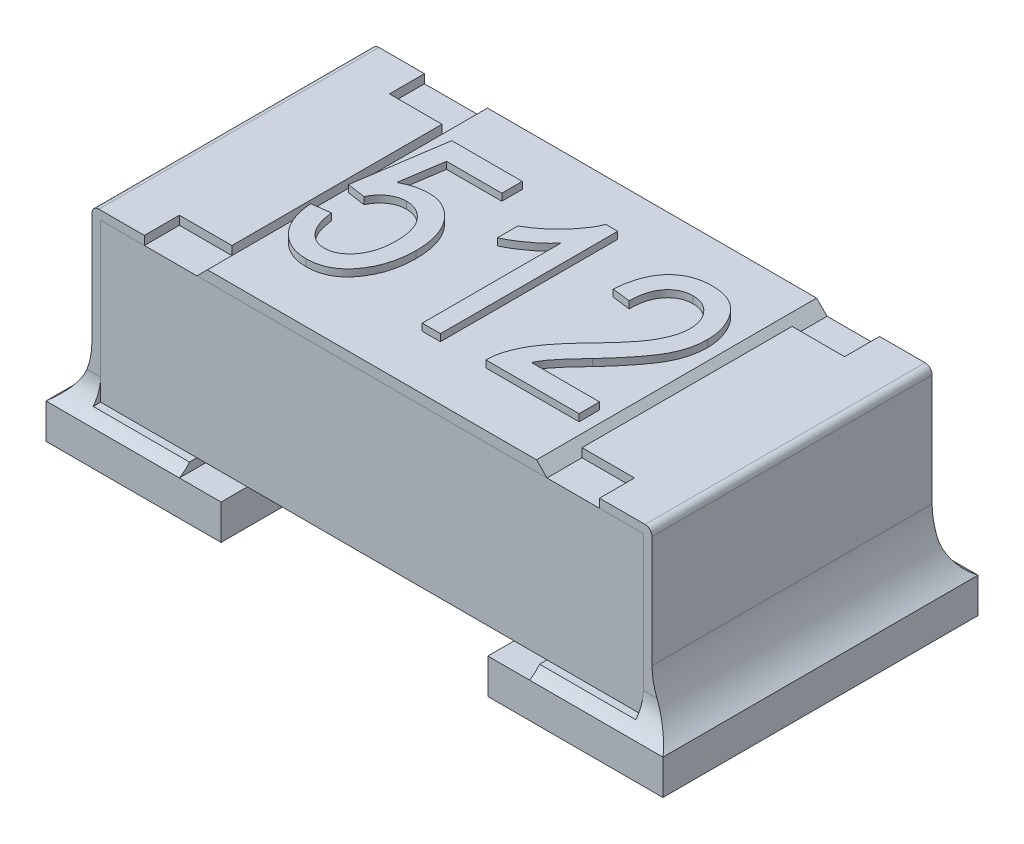
SolidWorks part; units mm, degrees
material "Ceramic Porcelain"
ref_plane "Front Plane" through (0, 0, 0) normal (0, 0, 1) x (1, 0, 0)
ref_plane "Top Plane" through (0, 0, 0) normal (0, 1, 0) x (1, 0, 0)
ref_plane "Right Plane" through (0, 0, 0) normal (1, 0, 0) x (0, 0, -1)
sketch "Sketch1" plane through (0, 0, 0) normal (1, 0, 0) x (0, 0, -1)
  line L0 (0, 55) -> (0, -55) construction
  line L1 (-0.4, 0.575) -> (0.4, 0.575)
  line L2 (-0.4, 0.575) -> (-0.4, 0.125)
  line L3 (-0.4, 0.125) -> (0.4, 0.125)
  line L4 (0.4, 0.575) -> (0.4, 0.125)
  line L5 (55, 0) -> (-55, 0) construction
  dimension "D1" = 0.8
  dimension "D2" = 0.4
  dimension "D3" = 0.45
  dimension "D4" = 0.125
extrude "Boss-Extrude1" add sketch "Sketch1" along normal mid plane 1.55
sketch "Sketch2" plane through (0, 0, 0) normal (0, 0, 1) x (1, 0, 0)
  line L0 (-0.5, 0.6) -> (-0.78, 0.6)
  line L1 (-0.8, 0.58) -> (-0.8, 0.1)
  line L2 (-0.8, 0.1) -> (-0.5, 0.1)
  line L3 (-0.5, 0.1) -> (-0.5, 0.125)
  line L4 (0.775, 0.125) -> (-0.775, 0.125) construction
  line L5 (-0.5, 0.125) -> (-0.775, 0.125)
  line L6 (-0.775, 0.125) -> (-0.775, 0.575)
  line L7 (-0.775, 0.575) -> (-0.5, 0.575)
  line L8 (0.775, 0.575) -> (-0.775, 0.575) construction
  line L9 (-0.5, 0.575) -> (-0.5, 0.6)
  line L11 (0.5, 0.575) -> (0.5, 0.6)
  line L12 (0.5, 0.6) -> (0.78, 0.6)
  line L13 (0.8, 0.58) -> (0.8, 0.1)
  line L14 (0.8, 0.1) -> (0.5, 0.1)
  line L15 (0.5, 0.1) -> (0.5, 0.125)
  line L16 (0.5, 0.125) -> (0.775, 0.125)
  line L17 (0.775, 0.125) -> (0.775, 0.575)
  line L18 (0.775, 0.575) -> (0.5, 0.575)
  arc A0 (0.78, 0.6) -> (0.8, 0.58) centre (0.78, 0.58) cw
  arc A1 (-0.78, 0.6) -> (-0.8, 0.58) centre (-0.78, 0.58) ccw
  point P28 (-0.8, 0.6)
  dimension "D6" = 0.02
  dimension "D1" = 0.025
  dimension "D2" = 0.025
  dimension "D3" = 0.025
  dimension "D4" = 0.3
  dimension "D5" = 0.3
extrude "Boss-Extrude2" add sketch "Sketch2" along normal mid plane 0.8 separate body
sketch "Sketch3" plane through (0, 0.6, 0) normal (0, 1, 0) x (1, 0, 0)
  line L0 (0.5, -0.4) -> (0.5, 0.4) construction
  line L1 (-0.5, 0.4) -> (-0.65, 0.4)
  line L2 (-0.5, 0.4) -> (-0.5, 0.3)
  line L3 (-0.5, 0.3) -> (-0.65, 0.3)
  line L4 (-0.65, 0.4) -> (-0.65, 0.3)
  line L5 (-0.5, -0.4) -> (-0.65, -0.4)
  line L6 (-0.5, -0.4) -> (-0.5, -0.3)
  line L7 (-0.5, -0.3) -> (-0.65, -0.3)
  line L8 (-0.65, -0.4) -> (-0.65, -0.3)
  line L9 (0.5, -0.4) -> (0.65, -0.4)
  line L10 (0.5, -0.4) -> (0.5, -0.3)
  line L11 (0.5, -0.3) -> (0.65, -0.3)
  line L12 (0.65, -0.4) -> (0.65, -0.3)
  line L13 (0.775, -0.4) -> (-0.775, -0.4) construction
  line L15 (0.5, 0.4) -> (0.65, 0.4)
  line L16 (0.5, 0.4) -> (0.5, 0.3)
  line L17 (0.5, 0.3) -> (0.65, 0.3)
  line L18 (0.65, 0.4) -> (0.65, 0.3)
  dimension "D1" = 0.15
  dimension "D2" = 0.1
extrude "Cut-Extrude1" cut sketch "Sketch3" against normal blind 0.025
sketch "Sketch4" plane through (0, 0, 0) normal (0, 0, 1) x (1, 0, 0)
  line L0 (-0.5, 0.575) -> (0.5, 0.575)
  line L1 (0.5, 0.575) -> (0.47, 0.605)
  line L2 (0.47, 0.605) -> (-0.47, 0.605)
  line L3 (-0.47, 0.605) -> (-0.5, 0.575)
  dimension "D1" = 45
  dimension "D2" = 45
  dimension "D3" = 0.03
extrude "Boss-Extrude3" add sketch "Sketch4" along normal mid plane 0.8 separate body
sketch "Sketch7" plane through (0, 0, 0) normal (0, 1, 0) x (1, 0, 0)
  line L0 (0, -0.2777) -> (0, 0.2777) construction
  line L1 (-0.381, -0.45) -> (-0.881, -0.45)
  line L2 (-0.381, -0.45) -> (-0.381, 0.45)
  line L3 (-0.381, 0.45) -> (-0.881, 0.45)
  line L4 (-0.881, -0.45) -> (-0.881, 0.45)
  line L5 (0.381, -0.45) -> (0.881, -0.45)
  line L6 (0.381, -0.45) -> (0.381, 0.45)
  line L7 (0.381, 0.45) -> (0.881, 0.45)
  line L8 (0.881, -0.45) -> (0.881, 0.45)
  line L9 (-0.2777, 0) -> (0.2777, 0) construction
  dimension "D1" = 0.5
  dimension "D2" = 0.381
  dimension "D3" = 0.381
  dimension "D4" = 0.9
  dimension "D5" = 0.45
extrude "Boss-Extrude5" add sketch "Sketch7" along normal blind 0.1
fillet "Fillet3" radius 0.2 1 edges at (-0.8, 0.1, 0)
fillet "Fillet4" radius 0.2 1 edges at (0.8, 0.1, 0)
fillet "Fillet5" radius 0.1 2 edges at (0.6905, 0.1, -0.4) (0.6905, 0.1, 0.4)
fillet "Fillet6" radius 0.1 2 edges at (-0.6905, 0.1, 0.4) (-0.6905, 0.1, -0.4)
sketch "Esquisse2" plane through (0, 0.605, 0) normal (0, 1, 0) x (1, 0, 0)
  text T0 "512" font "Arial Narrow" height 0.5
extrude "Boss.-Extru.1" add sketch "Esquisse2" along normal blind 0.02
